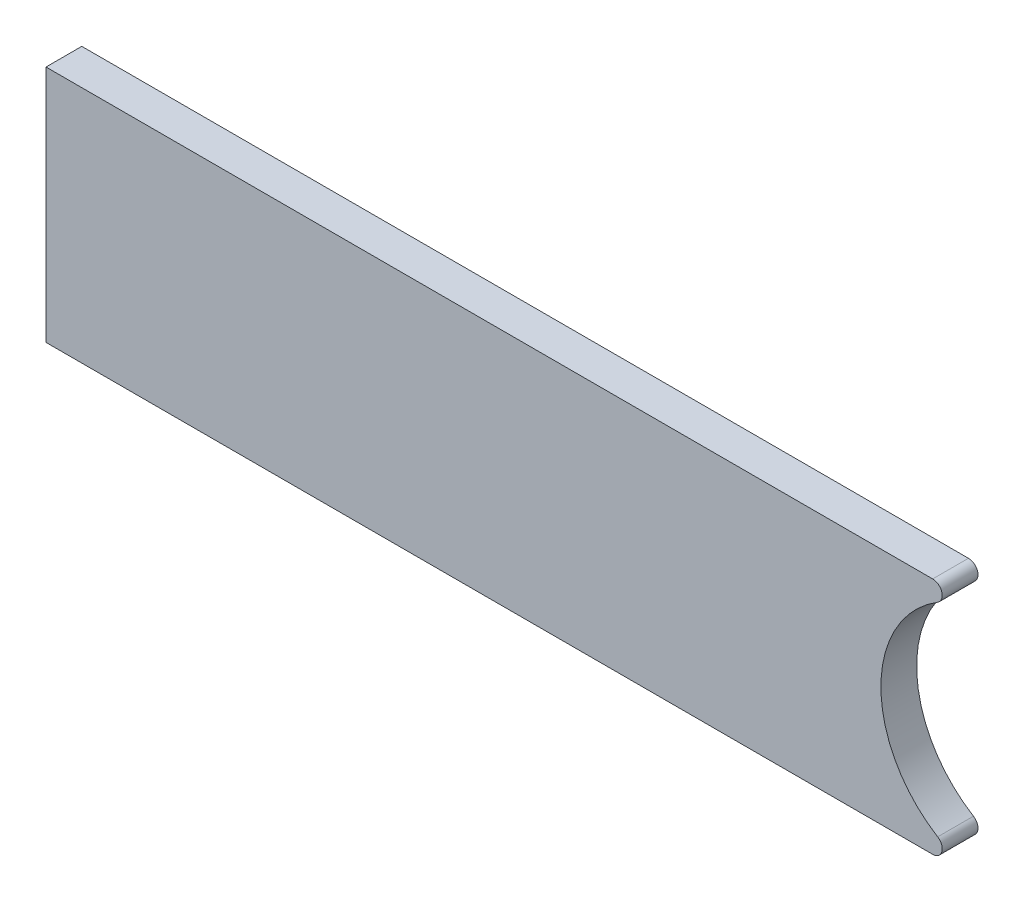
SolidWorks part; units mm, degrees
ref_plane "Plano frontal" through (0, 0, 0) normal (0, 0, 1) x (1, 0, 0)
ref_plane "Plano superior" through (0, 0, 0) normal (0, 1, 0) x (1, 0, 0)
ref_plane "Plano direito" through (0, 0, 0) normal (1, 0, 0) x (0, 0, -1)
sketch "Esboço1" plane through (0, 0, 0) normal (0, 0, 1) x (1, 0, 0)
  line L1 (-45.941, 28.3118) -> (34.059, 28.3118)
  line L2 (-45.941, 28.3118) -> (-45.941, 8.3118)
  line L3 (-45.941, 8.3118) -> (34.059, 8.3118)
  line L4 (34.059, 28.3118) -> (34.059, 8.3118)
  dimension "D1" = 80
  dimension "D2" = 20
extrude "Ressalto-extrusão1" add sketch "Esboço1" along normal blind 3
sketch "Esboço2" plane through (0, 0, 3) normal (0, 0, 1) x (1, 0, 0)
  line L0 (34.059, 8.3118) -> (34.059, 28.3118) construction
  circle A0 centre (34.059, 18.3118) radius 10
extrude "Corte-extrusão1" cut sketch "Esboço2" against normal blind 10
fillet "Filete1" radius 0.8 1 edges at (34.059, 28.3118, 1.5)
fillet "Filete2" radius 0.8 1 edges at (34.059, 8.3118, 1.5)
